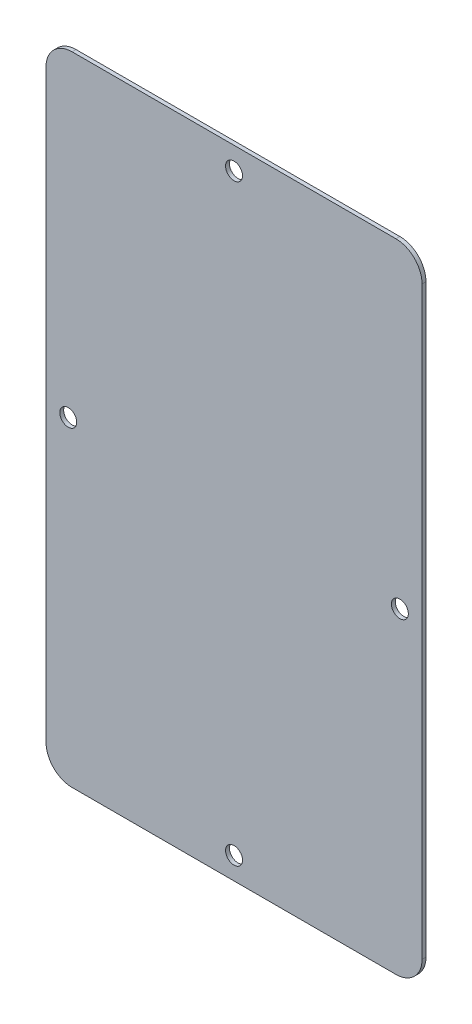
SolidWorks part; units mm, degrees
material "AISI 1045 Steel, cold drawn"
ref_plane "Front Plane" through (0, 0, 0) normal (0, 0, 1) x (1, 0, 0)
ref_plane "Top Plane" through (0, 0, 0) normal (0, 1, 0) x (1, 0, 0)
ref_plane "Right Plane" through (0, 0, 0) normal (1, 0, 0) x (0, 0, -1)
sketch "Sketch1" plane through (0, 0, 0) normal (0, 0, 1) x (1, 0, 0)
  line L1 (0, 0) -> (144, 0)
  line L2 (0, 0) -> (0, 244)
  line L3 (0, 244) -> (144, 244)
  line L4 (144, 0) -> (144, 244)
  dimension "D1" = 144
  dimension "D2" = 244
base flange "Base-Flange1" sketch "Sketch1" thickness 1.5 reverse thickness direction no parameters "D1"=0.7366
fillet "Fillet1" radius 10 4 edges at (0, 244, -0.75) (0, 0, -0.75) (144, 0, -0.75) (144, 244, -0.75)
sketch "Sketch6" plane through (0, 0, 0) normal (0, 0, 1) x (1, 0, 0)
  line L0 (134, 244) -> (10, 244) construction
  line L1 (144, 10) -> (144, 234) construction
  line L2 (0, 234) -> (0, 10) construction
  line L3 (10, 0) -> (134, 0) construction
  line L4 (10, 0) -> (134, 0) construction
  line L5 (144, 10) -> (144, 234) construction
  circle A0 centre (72, 235.5) radius 3.25
  circle A1 centre (72, 8.5) radius 3.25
  circle A2 centre (8.5, 122) radius 3.25
  circle A3 centre (135.5, 122) radius 3.25
  dimension "D1" = 8.5
  dimension "D2" = 8.5
  dimension "D3" = 8.5
  dimension "D4" = 8.5
  dimension "D5" = 6.5
  dimension "D6" = 6.5
  dimension "D7" = 6.5
  dimension "D8" = 6.5
  dimension "D9" = 122
  dimension "D10" = 122
  dimension "D11" = 72
  dimension "D12" = 72
extrude "Cut-Extrude1" cut sketch "Sketch6" against normal blind 10
sketch "Bend-Lines1" [suppressed] plane through (0, 0, 0) normal (0, 1, 0) x (1, 0, 0)
sketch "Bounding-Box1" [suppressed] plane through (0, 0, 0) normal (0, 1, 0) x (1, 0, 0)
sheet metal parameters "Sheet-Metal1" thickness 1.5 parameters "D1"=0.7366
flat pattern "Flat-Pattern1" [suppressed]
sketch "Bend-Lines2" plane through (0, 0, 0) normal (0, 1, 0) x (1, 0, 0)
sketch3d "Bounding-Box2" [suppressed]
  line L0 (145.5, 0, 0) -> (145.5, 245.5, 0) construction
  line L1 (0, 0, 0) -> (0, 245.5, 0) construction
  line L2 (145.5, 0, 0) -> (0, 0, 0) construction
  line L3 (145.5, 245.5, 0) -> (0, 245.5, 0) construction
sheet metal parameters "Sheet-Metal2" thickness 1.5 parameters "D1"=0.7366
flat pattern "Flat-Pattern1"
sketch "Bend-Lines2" plane through (0, 0, 0) normal (0, 1, 0) x (1, 0, 0)
sketch3d "Bounding-Box2" [suppressed]
  line L0 (144, 0, 0) -> (144, 244, 0) construction
  line L1 (0, 0, 0) -> (0, 244, 0) construction
  line L2 (144, 0, 0) -> (0, 0, 0) construction
  line L3 (144, 244, 0) -> (0, 244, 0) construction
